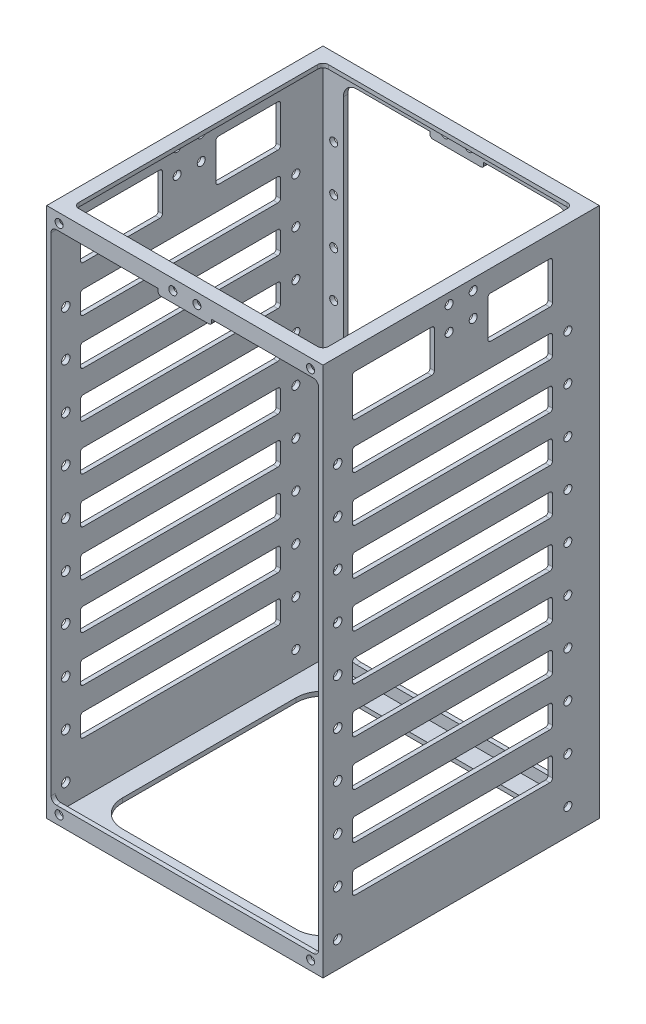
SolidWorks part; units mm, degrees
material "5052-H32"
ref_plane "Front Plane" through (0, 0, 0) normal (0, 0, 1) x (1, 0, 0)
ref_plane "Top Plane" through (0, 0, 0) normal (0, 1, 0) x (1, 0, 0)
ref_plane "Right Plane" through (0, 0, 0) normal (1, 0, 0) x (0, 0, -1)
sketch "Sketch1" plane through (0, 0, 0) normal (0, 1, 0) x (1, 0, 0)
  line L1 (-51.63, -51.63) -> (51.63, -51.63)
  line L2 (-51.63, -51.63) -> (-51.63, 51.63)
  line L3 (-51.63, 51.63) -> (51.63, 51.63)
  line L4 (51.63, -51.63) -> (51.63, 51.63)
  line L5 (-51.63, -51.63) -> (51.63, 51.63) construction
  line L6 (-51.63, 51.63) -> (51.63, -51.63) construction
  line L7 (-32.5, -42.5) -> (32.5, -42.5)
  line L8 (-42.5, -32.5) -> (-42.5, 32.5)
  line L9 (-32.5, 42.5) -> (32.5, 42.5)
  line L10 (42.5, -32.5) -> (42.5, 32.5)
  line L11 (-42.5, -42.5) -> (42.5, 42.5) construction
  line L12 (-42.5, 42.5) -> (42.5, -42.5) construction
  arc A0 (32.5, -42.5) -> (42.5, -32.5) centre (32.5, -32.5) ccw
  arc A1 (32.5, 42.5) -> (42.5, 32.5) centre (32.5, 32.5) cw
  arc A2 (-42.5, 32.5) -> (-32.5, 42.5) centre (-32.5, 32.5) cw
  arc A3 (-32.5, -42.5) -> (-42.5, -32.5) centre (-32.5, -32.5) cw
  point P0 (0, 0)
  point P6 (0, 0)
  dimension "D3" = 10
  dimension "D1" = 103.26
  dimension "D2" = 42.5
extrude "Boss-Extrude2" add sketch "Sketch1" along normal blind 1.63 contours A3 L7 A0 L10 A1 L9 A2 L8 | L2 L1 L4 L3 region at (0, 0, 0)
sketch "Sketch3" plane through (0, 1.63, 0) normal (0, 1, 0) x (1, 0, 0)
  line L1 (-51.63, -51.63) -> (51.63, -51.63)
  line L2 (-51.63, -51.63) -> (-51.63, 51.63)
  line L3 (-51.63, 51.63) -> (51.63, 51.63)
  line L4 (51.63, -51.63) -> (51.63, 51.63)
  line L5 (-51.63, -51.63) -> (51.63, 51.63) construction
  line L6 (-51.63, 51.63) -> (51.63, -51.63) construction
  line L7 (-50, -50) -> (50, -50)
  line L8 (-50, -50) -> (-50, 50)
  line L9 (-50, 50) -> (50, 50)
  line L10 (50, -50) -> (50, 50)
  line L11 (-50, -50) -> (50, 50) construction
  line L12 (-50, 50) -> (50, -50) construction
  point P0 (0, 0)
  point P7 (0, 0)
  dimension "D1" = 100
extrude "Boss-Extrude3" add sketch "Sketch3" along normal blind 196.74 contours L8 L7 L10 L9 | L2 L3 L4 L1
sketch "Sketch4" plane through (0, 0, -51.63) normal (0, 0, 1) x (1, 0, 0)
  line L0 (-51.63, 0) -> (51.63, 0) construction
  line L1 (-37.38, 6) -> (37.38, 6)
  line L2 (-42.38, 11) -> (-42.38, 187.37)
  line L3 (-37.38, 192.37) -> (37.38, 192.37)
  line L4 (42.38, 11) -> (42.38, 187.37)
  line L5 (-42.38, 6) -> (42.38, 192.37) construction
  line L6 (-42.38, 192.37) -> (42.38, 6) construction
  line L7 (51.63, 198.37) -> (51.63, 0) construction
  line L8 (-50, 198.37) -> (50, 198.37) construction
  line L9 (-51.63, 198.37) -> (-51.63, 0) construction
  arc A0 (-37.38, 6) -> (-42.38, 11) centre (-37.38, 11) cw
  arc A1 (37.38, 6) -> (42.38, 11) centre (37.38, 11) ccw
  arc A2 (37.38, 192.37) -> (42.38, 187.37) centre (37.38, 187.37) cw
  arc A3 (-42.38, 187.37) -> (-37.38, 192.37) centre (-37.38, 187.37) cw
  point P0 (0, 99.185)
  dimension "D5" = 5
  dimension "D1" = 6
  dimension "D2" = 9.25
  dimension "D3" = 6
  dimension "D4" = 9.25
extrude "Cut-Extrude1" cut sketch "Sketch4" along normal up to surface (1.63 mm away) up to face at (0, 100, -50)
sketch "Sketch5" plane through (0, 0, 51.63) normal (0, 0, 1) x (1, 0, 0)
  line L0 (-51.63, 198.37) -> (51.63, 198.37) construction
  line L1 (-48, 6.13) -> (48, 6.13)
  line L2 (-50, 8.13) -> (-50, 190.37)
  line L3 (-48, 192.37) -> (48, 192.37)
  line L4 (50, 8.13) -> (50, 190.37)
  line L5 (-50, 6.13) -> (50, 192.37) construction
  line L6 (-50, 192.37) -> (50, 6.13) construction
  line L7 (-51.63, 1.63) -> (51.63, 1.63) construction
  line L8 (-51.63, 198.37) -> (-51.63, 0) construction
  line L9 (51.63, 198.37) -> (51.63, 0) construction
  arc A0 (48, 6.13) -> (50, 8.13) centre (48, 8.13) ccw
  arc A1 (-48, 6.13) -> (-50, 8.13) centre (-48, 8.13) cw
  arc A2 (48, 192.37) -> (50, 190.37) centre (48, 190.37) cw
  arc A3 (-50, 190.37) -> (-48, 192.37) centre (-48, 190.37) cw
  point P0 (0, 99.25)
  dimension "D1" = 6
  dimension "D5" = 2
  dimension "D2" = 4.5
  dimension "D3" = 1.63
  dimension "D4" = 1.63
sketch "Sketch6" plane through (51.63, 0, 0) normal (1, 0, 0) x (0, 0, -1)
  line L0 (-51.63, 6.13) -> (-51.63, 192.37) construction
  line L2 (-51.63, 0) -> (51.63, 0) construction
  circle A0 centre (-46.13, 9.75) radius 1.6
  circle A1 centre (39.87, 9.75) radius 1.5
  circle A2 centre (-46.13, 26.85) radius 1.6
  circle A3 centre (39.87, 26.85) radius 1.5
  circle A4 centre (-46.13, 43.95) radius 1.6
  circle A5 centre (39.87, 43.95) radius 1.5
  circle A6 centre (-46.13, 61.05) radius 1.6
  circle A7 centre (39.87, 61.05) radius 1.5
  circle A8 centre (-46.13, 78.15) radius 1.6
  circle A9 centre (39.87, 78.15) radius 1.5
  circle A10 centre (-46.13, 95.25) radius 1.6
  circle A11 centre (39.87, 95.25) radius 1.5
  circle A12 centre (-46.13, 112.35) radius 1.6
  circle A13 centre (39.87, 112.35) radius 1.5
  circle A14 centre (-46.13, 129.45) radius 1.6
  circle A15 centre (39.87, 129.45) radius 1.5
  circle A16 centre (-46.13, 146.55) radius 1.6
  circle A17 centre (39.87, 146.55) radius 1.5
  circle A18 centre (-46.13, 163.65) radius 1.6
  circle A19 centre (39.87, 163.65) radius 1.5
  dimension "D4" = 3
  dimension "D5" = 3.2
  dimension "D1" = 5.5
  dimension "D2" = 86
  dimension "D3" = 9.75
  dimension "D7" = 17.1
  dimension "D9" = 17.1
  dimension "D6" = 9
  dimension "D8" = 2
extrude "Cut-Extrude2" cut sketch "Sketch6" against normal through all
extrude "Cut-Extrude3" cut sketch "Sketch5" against normal up to surface (1.63 mm away) up to face at (0, 100, 50)
sketch "Sketch7" plane through (51.63, 0, 0) normal (1, 0, 0) x (0, 0, -1)
  line L0 (-40.63, 38.95) -> (-40.63, 45.45)
  line L1 (-39.63, 20.85) -> (33.12, 20.85)
  line L2 (-40.63, 21.85) -> (-40.63, 28.35)
  line L3 (-39.63, 29.35) -> (33.12, 29.35)
  line L4 (34.12, 21.85) -> (34.12, 28.35)
  line L5 (-40.63, 20.85) -> (34.12, 29.35) construction
  line L6 (-40.63, 29.35) -> (34.12, 20.85) construction
  line L7 (-40.63, 158.65) -> (-40.63, 165.15)
  line L8 (-39.63, 37.95) -> (33.12, 37.95)
  line L9 (34.12, 38.95) -> (34.12, 45.45)
  line L10 (-39.63, 46.45) -> (33.12, 46.45)
  line L11 (-40.63, 56.05) -> (-40.63, 62.55)
  line L12 (-39.63, 55.05) -> (33.12, 55.05)
  line L13 (34.12, 56.05) -> (34.12, 62.55)
  line L14 (-39.63, 63.55) -> (33.12, 63.55)
  line L15 (-40.63, 73.15) -> (-40.63, 79.65)
  line L16 (-39.63, 72.15) -> (33.12, 72.15)
  line L17 (34.12, 73.15) -> (34.12, 79.65)
  line L18 (-39.63, 80.65) -> (33.12, 80.65)
  line L19 (-40.63, 90.25) -> (-40.63, 96.75)
  line L20 (-39.63, 89.25) -> (33.12, 89.25)
  line L21 (34.12, 90.25) -> (34.12, 96.75)
  line L22 (-39.63, 97.75) -> (33.12, 97.75)
  line L23 (-40.63, 107.35) -> (-40.63, 113.85)
  line L24 (-39.63, 106.35) -> (33.12, 106.35)
  line L25 (34.12, 107.35) -> (34.12, 113.85)
  line L26 (-39.63, 114.85) -> (33.12, 114.85)
  line L27 (-40.63, 124.45) -> (-40.63, 130.95)
  line L28 (-39.63, 123.45) -> (33.12, 123.45)
  line L29 (34.12, 124.45) -> (34.12, 130.95)
  line L30 (-39.63, 131.95) -> (33.12, 131.95)
  line L31 (-40.63, 141.55) -> (-40.63, 148.05)
  line L32 (-39.63, 140.55) -> (33.12, 140.55)
  line L33 (34.12, 141.55) -> (34.12, 148.05)
  line L34 (-39.63, 149.05) -> (33.12, 149.05)
  line L35 (-39.63, 157.65) -> (33.12, 157.65)
  line L36 (34.12, 158.65) -> (34.12, 165.15)
  line L37 (-39.63, 166.15) -> (33.12, 166.15)
  line L38 (-40.63, 141.55) -> (-40.63, 158.65) construction
  circle A0 centre (-46.13, 9.75) radius 1.6 construction
  arc A1 (33.12, 29.35) -> (34.12, 28.35) centre (33.12, 28.35) cw
  arc A2 (33.12, 20.85) -> (34.12, 21.85) centre (33.12, 21.85) ccw
  arc A3 (-39.63, 20.85) -> (-40.63, 21.85) centre (-39.63, 21.85) cw
  arc A4 (-40.63, 28.35) -> (-39.63, 29.35) centre (-39.63, 28.35) cw
  arc A5 (-40.63, 45.45) -> (-39.63, 46.45) centre (-39.63, 45.45) cw
  arc A6 (-39.63, 37.95) -> (-40.63, 38.95) centre (-39.63, 38.95) cw
  arc A7 (33.12, 37.95) -> (34.12, 38.95) centre (33.12, 38.95) ccw
  arc A8 (33.12, 46.45) -> (34.12, 45.45) centre (33.12, 45.45) cw
  arc A9 (-40.63, 62.55) -> (-39.63, 63.55) centre (-39.63, 62.55) cw
  arc A10 (-39.63, 55.05) -> (-40.63, 56.05) centre (-39.63, 56.05) cw
  arc A11 (33.12, 55.05) -> (34.12, 56.05) centre (33.12, 56.05) ccw
  arc A12 (33.12, 63.55) -> (34.12, 62.55) centre (33.12, 62.55) cw
  arc A13 (-40.63, 79.65) -> (-39.63, 80.65) centre (-39.63, 79.65) cw
  arc A14 (-39.63, 72.15) -> (-40.63, 73.15) centre (-39.63, 73.15) cw
  arc A15 (33.12, 72.15) -> (34.12, 73.15) centre (33.12, 73.15) ccw
  arc A16 (33.12, 80.65) -> (34.12, 79.65) centre (33.12, 79.65) cw
  arc A17 (-40.63, 96.75) -> (-39.63, 97.75) centre (-39.63, 96.75) cw
  arc A18 (-39.63, 89.25) -> (-40.63, 90.25) centre (-39.63, 90.25) cw
  arc A19 (33.12, 89.25) -> (34.12, 90.25) centre (33.12, 90.25) ccw
  arc A20 (33.12, 97.75) -> (34.12, 96.75) centre (33.12, 96.75) cw
  arc A21 (-40.63, 113.85) -> (-39.63, 114.85) centre (-39.63, 113.85) cw
  arc A22 (-39.63, 106.35) -> (-40.63, 107.35) centre (-39.63, 107.35) cw
  arc A23 (33.12, 106.35) -> (34.12, 107.35) centre (33.12, 107.35) ccw
  arc A24 (33.12, 114.85) -> (34.12, 113.85) centre (33.12, 113.85) cw
  arc A25 (-40.63, 130.95) -> (-39.63, 131.95) centre (-39.63, 130.95) cw
  arc A26 (-39.63, 123.45) -> (-40.63, 124.45) centre (-39.63, 124.45) cw
  arc A27 (33.12, 123.45) -> (34.12, 124.45) centre (33.12, 124.45) ccw
  arc A28 (33.12, 131.95) -> (34.12, 130.95) centre (33.12, 130.95) cw
  arc A29 (-40.63, 148.05) -> (-39.63, 149.05) centre (-39.63, 148.05) cw
  arc A30 (-39.63, 140.55) -> (-40.63, 141.55) centre (-39.63, 141.55) cw
  arc A31 (33.12, 140.55) -> (34.12, 141.55) centre (33.12, 141.55) ccw
  arc A32 (33.12, 149.05) -> (34.12, 148.05) centre (33.12, 148.05) cw
  arc A33 (-40.63, 165.15) -> (-39.63, 166.15) centre (-39.63, 165.15) cw
  arc A34 (-39.63, 157.65) -> (-40.63, 158.65) centre (-39.63, 158.65) cw
  circle A35 centre (39.87, 9.75) radius 1.5 construction
  arc A36 (33.12, 157.65) -> (34.12, 158.65) centre (33.12, 158.65) ccw
  arc A37 (33.12, 166.15) -> (34.12, 165.15) centre (33.12, 165.15) cw
  point P0 (-3.255, 25.1)
  dimension "D5" = 1
  dimension "D3" = 5.75
  dimension "D1" = 8.5
  dimension "D2" = 11.1
  dimension "D4" = 5.5
  dimension "D7" = 8.6
  dimension "D9" = 8.6
  dimension "D6" = 8
  dimension "D8" = 2
extrude "Cut-Extrude4" cut sketch "Sketch7" against normal through all
sketch "Sketch8" plane through (51.63, 0, 0) normal (1, 0, 0) x (0, 0, -1)
  line L7 (-51.63, 198.37) -> (51.63, 198.37) construction
  line L15 (-39.63, 190.37) -> (33.12, 190.37)
  line L16 (-40.63, 189.37) -> (-40.63, 175.75)
  line L17 (-39.63, 174.75) -> (33.12, 174.75)
  line L18 (34.12, 189.37) -> (34.12, 175.75)
  line L19 (33.12, 166.15) -> (-39.63, 166.15) construction
  arc A15 (33.12, 190.37) -> (34.12, 189.37) centre (33.12, 189.37) cw
  arc A16 (33.12, 174.75) -> (34.12, 175.75) centre (33.12, 175.75) ccw
  arc A17 (-40.63, 175.75) -> (-39.63, 174.75) centre (-39.63, 175.75) ccw
  arc A18 (-39.63, 190.37) -> (-40.63, 189.37) centre (-39.63, 189.37) ccw
  circle A19 centre (-46.13, 163.65) radius 1.6 construction
  circle A20 centre (39.87, 163.65) radius 1.5 construction
  point P0 (-2.625, 162.85)
  dimension "D6" = 1
  dimension "D2" = 8.6
  dimension "D8" = 8
  dimension "D9" = 5.5
  dimension "D10" = 5.75
extrude "Cut-Extrude5" cut sketch "Sketch8" against normal through all
sketch "Sketch15" plane through (51.63, 0, 0) normal (1, 0, 0) x (0, 0, -1)
  line L0 (-50, 198.37) -> (-50, 190.37) construction
  line L7 (33.12, 190.37) -> (-39.63, 190.37) construction
  line L8 (-10, 190.37) -> (10, 190.37)
  line L9 (-10, 190.37) -> (-10, 174.75)
  line L10 (-10, 174.75) -> (10, 174.75)
  line L11 (10, 190.37) -> (10, 174.75)
  line L12 (-39.63, 174.75) -> (33.12, 174.75) construction
  dimension "D1" = 20
  dimension "D2" = 40
extrude "Boss-Extrude4" add sketch "Sketch15" against normal up to surface (1.63 mm away) up to face at (50, 182.56, 3.255)
sketch "Sketch16" plane through (-51.63, 0, 0) normal (-1, 0, 0) x (0, 0, 1)
  line L7 (-10, 190.37) -> (10, 190.37)
  line L8 (-10, 190.37) -> (-10, 174.75)
  line L9 (-10, 174.75) -> (10, 174.75)
  line L10 (10, 190.37) -> (10, 174.75)
extrude "Boss-Extrude5" add sketch "Sketch16" against normal up to surface (1.63 mm away) up to face at (-50, 182.56, 3.255)
sketch "Sketch9" plane through (51.63, 0, 0) normal (1, 0, 0) x (0, 0, -1)
  line L0 (-51.63, 198.37) -> (51.63, 198.37) construction
  line L2 (-11.0428, 189.87) -> (9.2919, 189.87) construction
  line L3 (-50, 198.37) -> (-50, 190.37) construction
  circle A0 centre (-4.5, 194.37) radius 1.5
  circle A1 centre (4.5, 194.37) radius 1.5
  circle A2 centre (4.5, 185.37) radius 1.5
  circle A3 centre (-4.5, 185.37) radius 1.5
  dimension "D1" = 3
  dimension "D3" = 9
  dimension "D5" = 3
  dimension "D2" = 4
  dimension "D4" = 45.5
  dimension "D6" = 4.5
extrude "Cut-Extrude6" cut sketch "Sketch9" against normal through all
fillet "Fillet1" radius 1 8 edges at (-50.815, 174.75, 10) (-50.815, 190.37, 10) (-50.815, 190.37, -10) (-50.815, 174.75, -10) (50.815, 190.37, 10) (50.815, 174.75, 10) (50.815, 174.75, -10) (50.815, 190.37, -10)
sketch "Sketch18" plane through (0, 0, -51.63) normal (0, 0, -1) x (-1, 0, 0)
  line L0 (-37.38, 192.37) -> (37.38, 192.37) construction
  line L1 (-10, 192.37) -> (10, 192.37)
  line L2 (-10, 192.37) -> (-10, 191.37)
  line L3 (-9, 190.37) -> (9, 190.37)
  line L4 (10, 192.37) -> (10, 191.37)
  line L6 (-50, 198.37) -> (-50, 1.63) construction
  arc A0 (9, 190.37) -> (10, 191.37) centre (9, 191.37) ccw
  arc A1 (-10, 191.37) -> (-9, 190.37) centre (-9, 191.37) ccw
  point P4 (-10, 191.87)
  dimension "D3" = 1
  dimension "D1" = 2
  dimension "D2" = 20
  dimension "D4" = 40
extrude "Boss-Extrude7" add sketch "Sketch18" against normal up to surface (1.63 mm away) up to face at (0, 99.185, -50)
sketch "Sketch17" plane through (0, 0, 51.63) normal (0, 0, 1) x (1, 0, 0)
  line L0 (48, 192.37) -> (-48, 192.37) construction
  line L1 (-10, 192.37) -> (10, 192.37)
  line L2 (-10, 192.37) -> (-10, 191.37)
  line L3 (-9, 190.37) -> (9, 190.37)
  line L4 (10, 192.37) -> (10, 191.37)
  line L5 (-50, 198.37) -> (-50, 190.37) construction
  arc A0 (9, 190.37) -> (10, 191.37) centre (9, 191.37) ccw
  arc A1 (-10, 191.37) -> (-9, 190.37) centre (-9, 191.37) ccw
  dimension "D4" = 1
  dimension "D1" = 20
  dimension "D2" = 40
  dimension "D3" = 2
extrude "Boss-Extrude6" add sketch "Sketch17" against normal up to surface (1.63 mm away) up to face at (0, 193.8414, 50)
sketch "Sketch19" plane through (0, 0, 51.63) normal (0, 0, 1) x (1, 0, 0)
  line L0 (0, 198.37) -> (0, 190.37) construction
  line L1 (-9, 190.37) -> (9, 190.37) construction
  line L3 (-51.63, 198.37) -> (51.63, 198.37) construction
  circle A0 centre (-4.5, 194.37) radius 1.5
  circle A1 centre (4.5, 194.37) radius 1.5
  dimension "D1" = 3
  dimension "D2" = 4
  dimension "D3" = 4.5
extrude "Cut-Extrude7" cut sketch "Sketch19" against normal through all
sketch "Sketch20" plane through (0, 0, 51.63) normal (0, 0, 1) x (1, 0, 0)
  line L1 (-51.63, 0) -> (51.63, 0) construction
  line L2 (0, 198.37) -> (0, 0) construction
  line L3 (-51.63, 198.37) -> (51.63, 198.37) construction
  line L4 (-50, 198.37) -> (-50, 190.37) construction
  line L5 (-50, 8.13) -> (-50, 1.63) construction
  circle A0 centre (-46.98, 3.5) radius 1.5
  circle A1 centre (-46.98, 194.87) radius 1.5
  circle A2 centre (46.98, 3.5) radius 1.5
  circle A3 centre (46.98, 194.87) radius 1.5
  dimension "D1" = 3
  dimension "D4" = 3
  dimension "D2" = 3.02
  dimension "D3" = 3.5
  dimension "D5" = 3.02
  dimension "D6" = 3.5
extrude "Cut-Extrude8" cut sketch "Sketch20" against normal up to surface (1.63 mm away) up to face at (-6, 194.37, 50)
sketch "Sketch23" plane through (0, 0, -51.63) normal (0, 0, -1) x (-1, 0, 0)
  line L0 (-51.63, 198.37) -> (-51.63, 0) construction
  line L1 (51.63, 0) -> (-51.63, 0) construction
  line L2 (0, 198.37) -> (0, 0) construction
  line L3 (51.63, 198.37) -> (-51.63, 198.37) construction
  circle A0 centre (-46, 17.05) radius 1.5
  circle A2 centre (-46, 34.15) radius 1.5
  circle A3 centre (-46, 51.25) radius 1.5
  circle A4 centre (-46, 68.35) radius 1.5
  circle A5 centre (-46, 85.45) radius 1.5
  circle A6 centre (-46, 102.55) radius 1.5
  circle A7 centre (-46, 119.65) radius 1.5
  circle A8 centre (-46, 136.75) radius 1.5
  circle A9 centre (-46, 153.85) radius 1.5
  circle A10 centre (-46, 170.95) radius 1.5
  circle A11 centre (46, 170.95) radius 1.5
  circle A12 centre (46, 153.85) radius 1.5
  circle A13 centre (46, 136.75) radius 1.5
  circle A14 centre (46, 119.65) radius 1.5
  circle A15 centre (46, 102.55) radius 1.5
  circle A16 centre (46, 85.45) radius 1.5
  circle A17 centre (46, 68.35) radius 1.5
  circle A18 centre (46, 51.25) radius 1.5
  circle A19 centre (46, 34.15) radius 1.5
  circle A20 centre (46, 17.05) radius 1.5
  dimension "D1" = 3
  dimension "D2" = 5.63
  dimension "D3" = 17.05
  dimension "D5" = 17.1
  dimension "D4" = 10
extrude "Cut-Extrude10" cut sketch "Sketch23" against normal up to surface (1.63 mm away) up to face at (-6, 194.37, -50)
sketch "Sketch25" plane through (0, 198.37, 0) normal (0, 1, 0) x (1, 0, 0)
  line L1 (-50, -50) -> (50, -50)
  line L2 (-50, -50) -> (-50, 50)
  line L3 (-50, 50) -> (50, 50)
  line L4 (50, -50) -> (50, 50)
  line L5 (-50, -50) -> (50, 50) construction
  line L6 (-50, 50) -> (50, -50) construction
  point P0 (0, 0)
extrude "Boss-Extrude8" add sketch "Sketch25" against normal blind 1.5
sketch "Sketch26" plane through (0, 198.37, 0) normal (0, 1, 0) x (1, 0, 0)
  line L0 (-51.63, -51.63) -> (-51.63, 51.63) construction
  line L1 (-44.63, -46.63) -> (44.63, -46.63)
  line L2 (-46.63, -44.63) -> (-46.63, 44.63)
  line L3 (-44.63, 46.63) -> (44.63, 46.63)
  line L4 (46.63, -44.63) -> (46.63, 44.63)
  line L5 (-46.63, -46.63) -> (46.63, 46.63) construction
  line L6 (-46.63, 46.63) -> (46.63, -46.63) construction
  arc A0 (-46.63, 44.63) -> (-44.63, 46.63) centre (-44.63, 44.63) cw
  arc A1 (44.63, 46.63) -> (46.63, 44.63) centre (44.63, 44.63) cw
  arc A2 (44.63, -46.63) -> (46.63, -44.63) centre (44.63, -44.63) ccw
  arc A3 (-44.63, -46.63) -> (-46.63, -44.63) centre (-44.63, -44.63) cw
  point P0 (0, 0)
  dimension "D2" = 2
  dimension "D1" = 5
extrude "Cut-Extrude11" cut sketch "Sketch26" against normal up to surface (1.5 mm away) up to face at (0, 196.87, 0)
equation "\"D2@Sketch4\"=\"D4@Sketch4\""
equation "\"D4@Sketch5\"=\"D3@Sketch5\""
